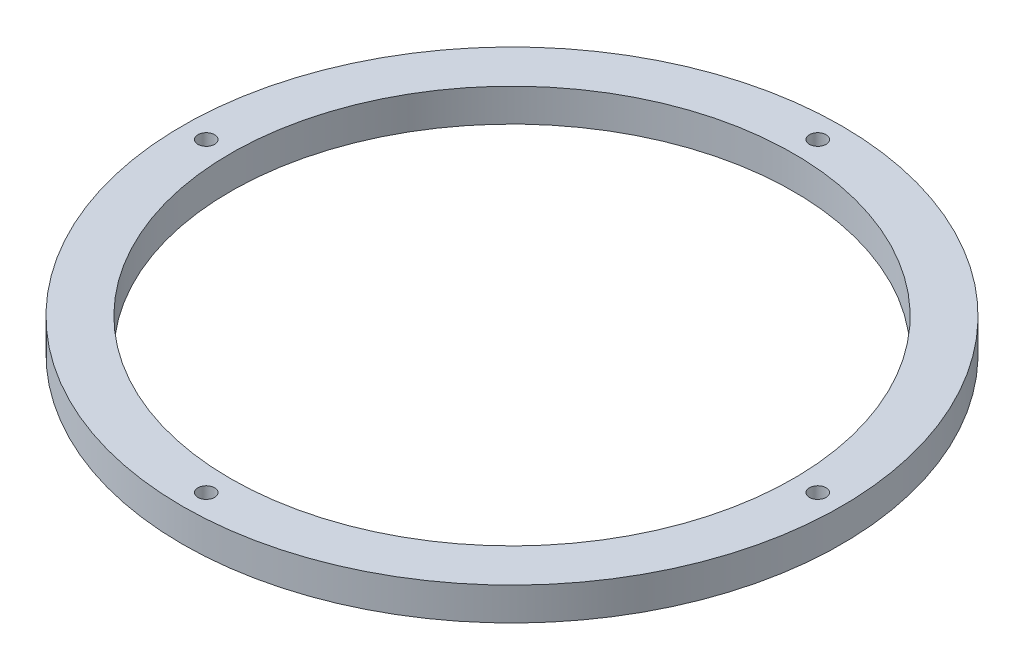
SolidWorks part; units mm, degrees
ref_plane "Front Plane" through (0, 0, 0) normal (0, 0, 1) x (1, 0, 0)
ref_plane "Top Plane" through (0, 0, 0) normal (0, 1, 0) x (1, 0, 0)
ref_plane "Right Plane" through (0, 0, 0) normal (1, 0, 0) x (0, 0, -1)
sketch "Sketch1" plane through (0, 0, 0) normal (0, 1, 0) x (1, 0, 0)
  circle A0 centre (0, 0) radius 100.375
  circle A5 centre (0, 0) radius 85.75
  dimension "D1" = 200.75
  dimension "D2" = 171.5
extrude "Boss-Extrude1" add sketch "Sketch1" along normal mid plane 10
sketch "Sketch2" plane through (0, 0, 0) normal (0, 1, 0) x (1, 0, 0)
  circle A0 centre (-93.125, 0) radius 1.27
  point P2 (0, 0)
  dimension "D2" = 2.54
  dimension "D1" = 93.125
extrude "Cut-Extrude1" cut sketch "Sketch2" against normal through all both and the other way through all
ref_axis "Axis1" through (0, 5.5, 0) along (0, -1, 0)
pattern_circular "CirPattern1" count 4 over 360 about axis through (0, 5.5, 0) along (0, -1, 0) of "Cut-Extrude1"
hole_wizard "CSK for #10 Flat Head Machine Screw (100)1" positions "3DSketch1" profile "Sketch3" countersink size "#10" standard "ANSI Inch" end condition through all
sketch3d "3DSketch1"
  line L0 (93.125, -5, 0) -> (93.125, 5, 0) construction
  line L1 (0, -5, -93.125) -> (0, 5, -93.125) construction
  line L2 (-93.125, -5, 0) -> (-93.125, 5, 0) construction
  line L3 (0, -5, 93.125) -> (0, 5, 93.125) construction
  point P0 (93.125, -5, 0)
  point P4 (0, -5, -93.125)
  point P8 (-93.125, -5, 0)
  point P12 (0, -5, 93.125)
sketch "Sketch3" plane through (93.125, -5, 0) normal (1, 0, 0) x (0, 0, -1)
  line L0 (0, 0) -> (0, 10)
  line L1 (0, 10) -> (2.5527, 10)
  line L2 (2.5527, 10) -> (2.5527, 1.9608)
  line L3 (2.5527, 1.9608) -> (4.8895, 0)
  line L5 (4.8895, 0) -> (0, 0)
  line L6 (-2.5527, 1.9608) -> (-4.8895, 0) construction
  line L11 (0, -6.35) -> (0, 107.95) construction
  dimension "Thru Hole Dia." = 5.1054
  dimension "Thru Hole Depth" = 10
  dimension "Near C'Sink Dia." = 9.779
  dimension "Near C'Sink Angle" = 100
equation "\"thicknes\" = 10mm"
equation "\"D1@Boss-Extrude1\"=\"thicknes\""
equation "\"id\" = 171.5mm"
equation "\"D2@Sketch1\"=\"id\""
equation "\"od\" = 200.75mm"
equation "\"D1@Sketch1\"=\"od\""
equation "\"hole_radius\"= \"hole_diameter\" / 2"
equation "\"D1@Sketch2\"=\"hole_radius\""
equation "\"hole_diameter\" = 186.25mm"
